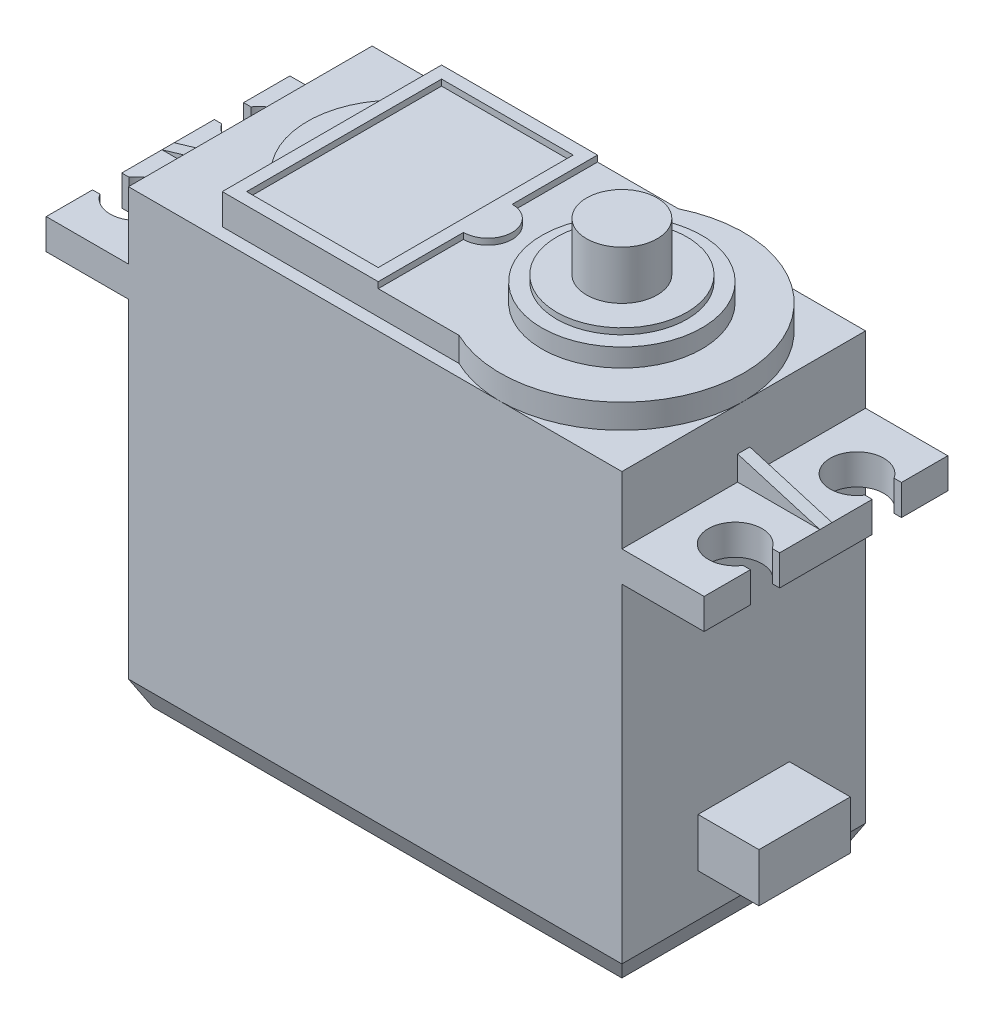
SolidWorks part; units mm, degrees
ref_plane "前视基准面" through (0, 0, 0) normal (0, 0, 1) x (1, 0, 0)
ref_plane "上视基准面" through (0, 0, 0) normal (0, 1, 0) x (1, 0, 0)
ref_plane "右视基准面" through (0, 0, 0) normal (1, 0, 0) x (0, 0, -1)
sketch "草图1" plane through (0, 0, 0) normal (0, 1, 0) x (1, 0, 0)
  line L1 (-20.25, 10) -> (20.25, 10)
  line L2 (-20.25, 10) -> (-20.25, -10)
  line L3 (-20.25, -10) -> (20.25, -10)
  line L4 (20.25, 10) -> (20.25, -10)
  line L5 (-20.25, 10) -> (20.25, -10) construction
  line L6 (-20.25, -10) -> (20.25, 10) construction
  point P0 (0, 0)
  dimension "D1" = 40.5
  dimension "D2" = 20
extrude "凸台-拉伸1" add sketch "草图1" along normal blind 37
sketch "草图2" plane through (0, 37, 0) normal (0, 1, 0) x (1, 0, 0)
  line L0 (20.25, 10) -> (-20.25, 10) construction
  line L1 (20.25, -10) -> (20.25, 10) construction
  line L2 (-20.25, -10) -> (20.25, -10) construction
  line L3 (-13.55, 9) -> (5.8911, 9)
  line L4 (5.8911, -9) -> (-13.55, -9)
  line L5 (-13.55, 9) -> (-13.55, 5)
  line L6 (-13.55, -5) -> (-13.55, -9)
  arc A0 (5.8911, -9) -> (5.8911, 9) centre (10.25, 0) ccw
  arc A1 (-13.55, 5) -> (-13.55, -5) centre (-8.3, 0) ccw
  point P17 (-15.55, 0)
  dimension "D5" = 2
  dimension "D1" = 1
  dimension "D2" = 1
  dimension "D3" = 33.8
  dimension "D4" = 10
  dimension "D6" = 4
extrude "凸台-拉伸2" add sketch "草图2" along normal blind 2
sketch "草图3" plane through (0, 39, 0) normal (0, 1, 0) x (1, 0, 0)
  line L0 (-13.55, -9) -> (5.8911, -9) construction
  line L1 (-13.55, 9) -> (-0.75, 9)
  line L2 (-13.55, 9) -> (-13.55, -9)
  line L3 (-13.55, -9) -> (-0.75, -9)
  line L4 (-0.75, 9) -> (-0.75, 2)
  line L5 (-0.75, -2) -> (-0.75, -9)
  line L6 (-12.55, 8) -> (-1.75, 8)
  line L7 (-12.55, 8) -> (-12.55, -8)
  line L8 (-12.55, -8) -> (-1.75, -8)
  line L9 (-1.75, 8) -> (-1.75, -8)
  arc A0 (-0.75, -2) -> (-0.75, 2) centre (-0.75, 0) ccw
  dimension "D6" = 2
  dimension "D1" = 12.8
  dimension "D2" = 1
  dimension "D3" = 1
  dimension "D4" = 1
  dimension "D5" = 1
extrude "凸台-拉伸3" add sketch "草图3" along normal blind 0.5
sketch "草图4" plane through (0, 39, 0) normal (0, 1, 0) x (1, 0, 0)
  circle A0 centre (10.25, 0) radius 6.575
  dimension "D1" = 13.15
extrude "凸台-拉伸4" add sketch "草图4" along normal blind 1.5
sketch "草图5" plane through (0, 40.5, 0) normal (0, 1, 0) x (1, 0, 0)
  circle A0 centre (10.25, 0) radius 5.35
  dimension "D1" = 10.7
extrude "凸台-拉伸5" add sketch "草图5" along normal blind 0.5
sketch "草图6" plane through (0, 41, 0) normal (0, 1, 0) x (1, 0, 0)
  circle A0 centre (10.25, 0) radius 2.9
  dimension "D1" = 5.8
extrude "凸台-拉伸6" add sketch "草图6" along normal blind 4
sketch "草图7" plane through (-20.25, 0, 0) normal (-1, 0, 0) x (0, 0, 1)
  line L0 (-10, 37) -> (-10, 0) construction
  line L1 (-10, 31.5) -> (10, 31.5)
  line L2 (-10, 31.5) -> (-10, 29)
  line L3 (-10, 29) -> (10, 29)
  line L4 (10, 31.5) -> (10, 29)
  line L5 (10, 37) -> (10, 0) construction
  line L7 (-10, 0) -> (10, 0) construction
  dimension "D1" = 29
  dimension "D2" = 2.5
extrude "凸台-拉伸7" add sketch "草图7" along normal blind 6.75
sketch "草图8" plane through (0, 31.5, 0) normal (0, 1, 0) x (1, 0, 0)
  line L3 (-20.25, 10) -> (-20.25, -10) construction
  line L4 (-27, 10) -> (-20.25, 10) construction
  line L5 (-27, -10) -> (-27, 10) construction
  line L6 (-27, 6.2) -> (-26.3939, 6.2)
  line L7 (-27, 6.2) -> (-27, 3.8)
  line L8 (-27, 3.8) -> (-26.3939, 3.8)
  line L11 (-27, -3.8) -> (-26.3939, -3.8)
  line L12 (-27, -3.8) -> (-27, -6.2)
  line L13 (-27, -6.2) -> (-26.3939, -6.2)
  arc A0 (-26.3939, 3.8) -> (-26.3939, 6.2) centre (-24.55, 5) ccw
  arc A1 (-26.3939, -6.2) -> (-26.3939, -3.8) centre (-24.55, -5) ccw
  point P18 (-27, -5)
  point P19 (-27, 5)
  dimension "D4" = 4.4
  dimension "D5" = 4.4
  dimension "D1" = 10
  dimension "D2" = 4.3
  dimension "D3" = 4.3
  dimension "D6" = 5
  dimension "D7" = 2.4
  dimension "D8" = 2.4
extrude "切除-拉伸1" cut sketch "草图8" against normal blind 7
ref_plane "基准面1" through (0, 0, 0) normal (0, 0, 1) x (1, 0, 0)
sketch "草图10" plane through (0, 0, 0) normal (0, 0, 1) x (1, 0, 0)
  line L0 (-20.25, 33.5) -> (-27, 31.5)
  line L1 (-20.25, 37) -> (-20.25, 31.5) construction
  line L2 (-27, 31.5) -> (-20.25, 31.5) construction
  dimension "D1" = 2
rib "筋1" sketch "草图10" sketch "草图10" thickness 1 extrusion direction parallel to sketch draft on no parameters "D1"=1
ref_plane "基准面3" through (0, 0, 0) normal (-1, 0, 0) x (0, 0, 1)
mirror "镜向1" about plane through (0, 0, 0) normal (-1, 0, 0) of "切除-拉伸1", "凸台-拉伸7", "筋1"
sketch "草图13" plane through (20.25, 0, 0) normal (1, 0, 0) x (0, 0, -1)
  line L0 (3.8, 29) -> (-3.8, 29) construction
  line L1 (-3.75, 9.5) -> (3.75, 9.5)
  line L2 (-3.75, 9.5) -> (-3.75, 5.5)
  line L3 (-3.75, 5.5) -> (3.75, 5.5)
  line L4 (3.75, 9.5) -> (3.75, 5.5)
  line L5 (-3.75, 9.5) -> (3.75, 5.5) construction
  line L6 (-3.75, 5.5) -> (3.75, 9.5) construction
  point P0 (0, 7.5)
  dimension "D1" = 7.5
  dimension "D2" = 19.5
  dimension "D3" = 4
extrude "凸台-拉伸9" add sketch "草图13" along normal blind 5
chamfer "倒角1" distance 1 distance2 2 4 edges at (20.25, 0, 0) (0, 0, 10) (-20.25, 0, 0) (0, 0, -10) first distance on face at (0, 0, 0)
